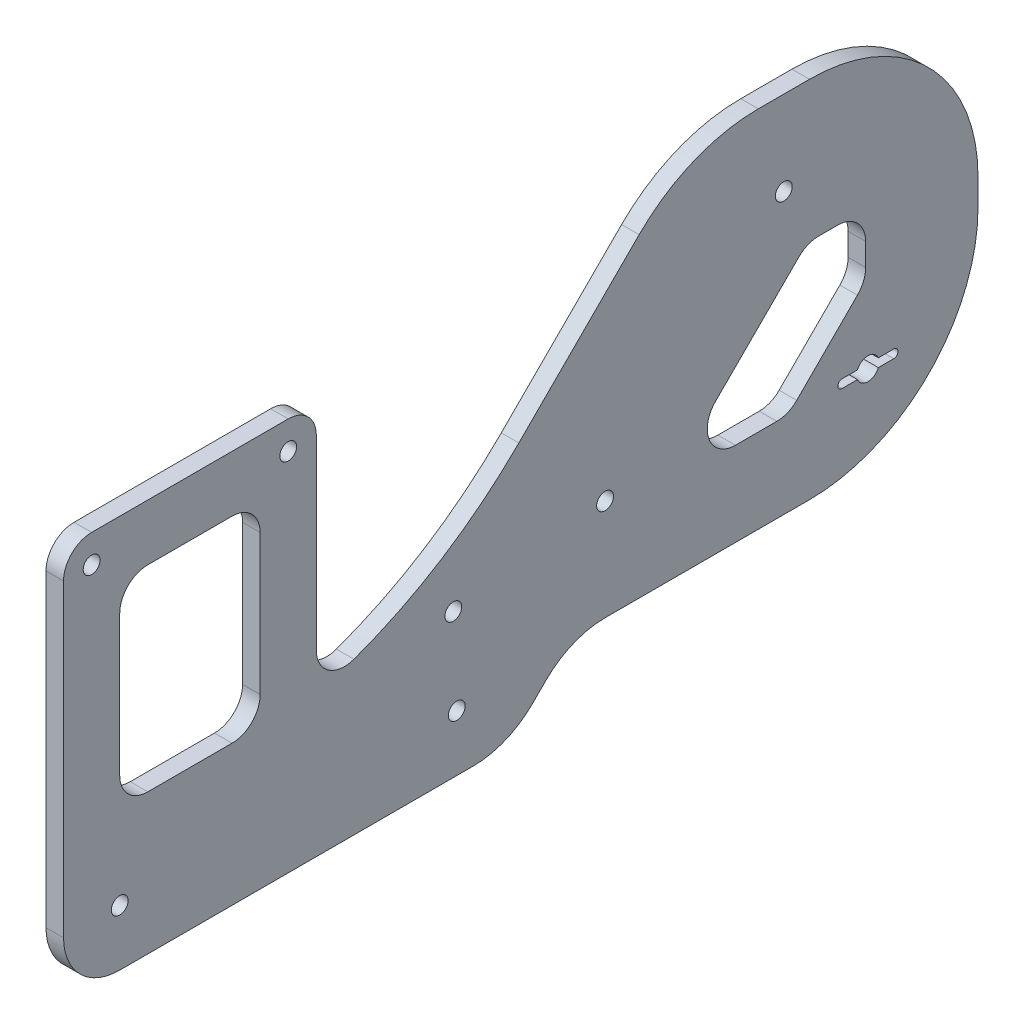
SolidWorks part; units mm, degrees
ref_plane "Front Plane" through (0, 0, 0) normal (0, 0, 1) x (1, 0, 0)
ref_plane "Top Plane" through (0, 0, 0) normal (0, 1, 0) x (1, 0, 0)
ref_plane "Right Plane" through (0, 0, 0) normal (1, 0, 0) x (0, 0, -1)
sketch "Sketch1" plane through (0, 0, 0) normal (1, 0, 0) x (0, 0, -1)
  line L0 (-62.0729, -10) -> (29.851, 81.9239) construction
  line L1 (29.851, 81.9239) -> (22.0729, 89.7021) construction
  line L2 (22.0729, 89.7021) -> (-69.851, -2.2218) construction
  line L3 (-69.851, -2.2218) -> (-62.0729, -10) construction
  line L4 (-4.6, 0) -> (4.6, 0) construction
  line L5 (-6, 5) -> (-6, -5) construction
  line L6 (-4.6, 0.75) -> (-1.854, 0.75)
  line L7 (-4.6, -0.75) -> (-1.854, -0.75)
  line L8 (-6, -5) -> (6, -5) construction
  line L9 (1.854, 0.75) -> (4.6, 0.75)
  line L10 (1.854, -0.75) -> (4.6, -0.75)
  line L11 (6, -5) -> (6, 5) construction
  line L12 (6, 5) -> (-6, 5) construction
  line L13 (-6, 5) -> (6, -5) construction
  line L14 (-69.851, -2.2218) -> (29.851, 81.9239) construction
  line L15 (-20, 39.851) -> (-20, 79.8794) construction
  line L16 (-9.747, 57.8823) -> (-1.9688, 50.1041) construction
  line L17 (-46.7993, 3.0108) -> (-14.9795, 34.8306) construction
  line L18 (-73.2042, -16.1314) -> (-133.2042, -16.1314) construction
  line L19 (-73.8108, -0.5248) -> (-63.2042, -11.1314) construction
  line L20 (-62.0729, -10) -> (-63.2042, -11.1314) construction
  line L21 (-143.2042, -1.1314) -> (-143.2042, -26.1314)
  line L22 (-143.2042, -26.1314) -> (-64.0621, -26.1314)
  line L23 (-64.0621, -26.1314) -> (-52.9307, -15)
  line L24 (-52.9307, -15) -> (19.6, -15)
  line L25 (19.6, -15) -> (19.6, 49.8306)
  line L26 (19.6, 49.8306) -> (-31.9408, 49.8306)
  line L27 (-31.9408, 49.8306) -> (-82.9027, -1.1314)
  line L28 (-82.9027, -1.1314) -> (-98.2042, -1.1314)
  line L29 (0, -31) -> (-153.4899, -31) construction
  line L30 (-35.668, 0) -> (-10.8374, 24.8306)
  line L31 (-10.8374, 24.8306) -> (-0.4, 24.8306)
  line L32 (-0.4, 24.8306) -> (-0.4, 13.7421)
  line L33 (-0.4, 13.7421) -> (-14.1421, 0)
  line L34 (-14.1421, 0) -> (-35.668, 0)
  line L35 (-143.2042, -1.1314) -> (-98.2042, -1.1314) construction
  line L36 (-143.2042, 38.8686) -> (-98.2042, 38.8686) construction
  line L37 (-143.2042, -1.1314) -> (-143.2042, 43.8686)
  line L38 (-143.2042, 43.8686) -> (-98.2042, 43.8686)
  line L39 (-98.2042, -1.1314) -> (-98.2042, 43.8686)
  line L40 (-143.2042, -1.1314) -> (-98.2042, 43.8686) construction
  line L41 (-143.2042, 43.8686) -> (-98.2042, -1.1314) construction
  line L42 (-138.2042, 38.8686) -> (-120.7042, 43.8686) construction
  line L43 (-120.7042, 43.8686) -> (-103.2042, 38.8686) construction
  line L44 (-120.7042, 16.3686) -> (-120.7042, 21.3686) construction
  line L45 (-133.2042, 33.8686) -> (-108.2042, 33.8686)
  line L46 (-133.2042, 33.8686) -> (-133.2042, -1.1314)
  line L47 (-133.2042, -1.1314) -> (-108.2042, -1.1314)
  line L48 (-108.2042, 33.8686) -> (-108.2042, -1.1314)
  line L49 (-133.2042, 33.8686) -> (-108.2042, -1.1314) construction
  line L50 (-133.2042, -1.1314) -> (-108.2042, 33.8686) construction
  arc A0 (-1.854, -0.75) -> (1.854, -0.75) centre (0, 0) ccw
  arc A1 (-4.6, 0.75) -> (-4.6, -0.75) centre (-4.6, 0) ccw
  arc A2 (1.854, 0.75) -> (-1.854, 0.75) centre (0, 0) ccw
  circle A3 centre (0, 0) radius 31 construction
  arc A4 (4.6, -0.75) -> (4.6, 0.75) centre (4.6, 0) ccw
  circle A5 centre (-46.7993, 3.0108) radius 1.5
  circle A6 centre (-14.9795, 34.8306) radius 1.5
  circle A7 centre (-73.8108, -0.5248) radius 1.5
  circle A8 centre (-73.2042, -16.1314) radius 1.5
  circle A9 centre (-133.2042, -16.1314) radius 1.5
  circle A10 centre (-138.2042, 38.8686) radius 1.5
  circle A11 centre (-103.2042, 38.8686) radius 1.5
  point P11 (-4.6, 0)
  point P16 (4.6, 0)
  point P57 (-120.7042, 21.3686)
  point P69 (-120.7042, 16.3686)
  dimension "D4" = 4
  dimension "D5" = 0.75
  dimension "D9" = 62
  dimension "D14" = 3
  dimension "D15" = 1.6
  dimension "D1" = 11
  dimension "D2" = 130
  dimension "D3" = 9.2
  dimension "D6" = 10
  dimension "D7" = 12
  dimension "D8" = 45
  dimension "D10" = 20
  dimension "D11" = 10
  dimension "D12" = 45
  dimension "D13" = 1.6
  dimension "D16" = 20
  dimension "D17" = 65
  dimension "D18" = 15
  dimension "D19" = 5
  dimension "D20" = 10
  dimension "D21" = 60
  dimension "D22" = 10
  dimension "D23" = 15
  dimension "D24" = 10
  dimension "D25" = 15
  dimension "D26" = 10
  dimension "D27" = 15
  dimension "D28" = 15
  dimension "D29" = 10
  dimension "D30" = 45
  dimension "D31" = 10
  dimension "D32" = 10
  dimension "D33" = 15
  dimension "D34" = 20
  dimension "D35" = 25
  dimension "D36" = 45
  dimension "D37" = 45
  dimension "D38" = 5
  dimension "D39" = 5
  dimension "D40" = 10
  dimension "D41" = 35
extrude "Boss-Extrude1" add sketch "Sketch1" along normal blind 3.125
fillet "Fillet2" radius 15 2 edges at (1.5625, -26.1314, 64.0621) (1.5625, -15, 52.9307)
fillet "Fillet3" radius 30 1 edges at (1.5625, -15, -19.6)
fillet "Fillet4" radius 30 1 edges at (1.5625, 49.8306, 31.9408)
fillet "Fillet5" radius 80 1 edges at (1.5625, -1.1314, 82.9027)
fillet "Fillet6" radius 30 1 edges at (1.5625, 49.8306, -19.6)
fillet "Fillet7" radius 5 5 edges at (1.5625, 0, 35.668) (1.5625, 24.8306, 10.8374) (1.5625, 24.8306, 0.4) (1.5625, 13.7421, 0.4) (1.5625, 0, 14.1421)
fillet "Fillet1" radius 10 1 edges at (1.5625, -26.1314, 143.2042)
fillet "Fillet8" radius 5 7 edges at (1.5625, -1.1314, 98.2042) (1.5625, 43.8686, 98.2042) (1.5625, 43.8686, 143.2042) (1.5625, -1.1314, 133.2042) (1.5625, -1.1314, 108.2042) (1.5625, 33.8686, 108.2042) (1.5625, 33.8686, 133.2042)
